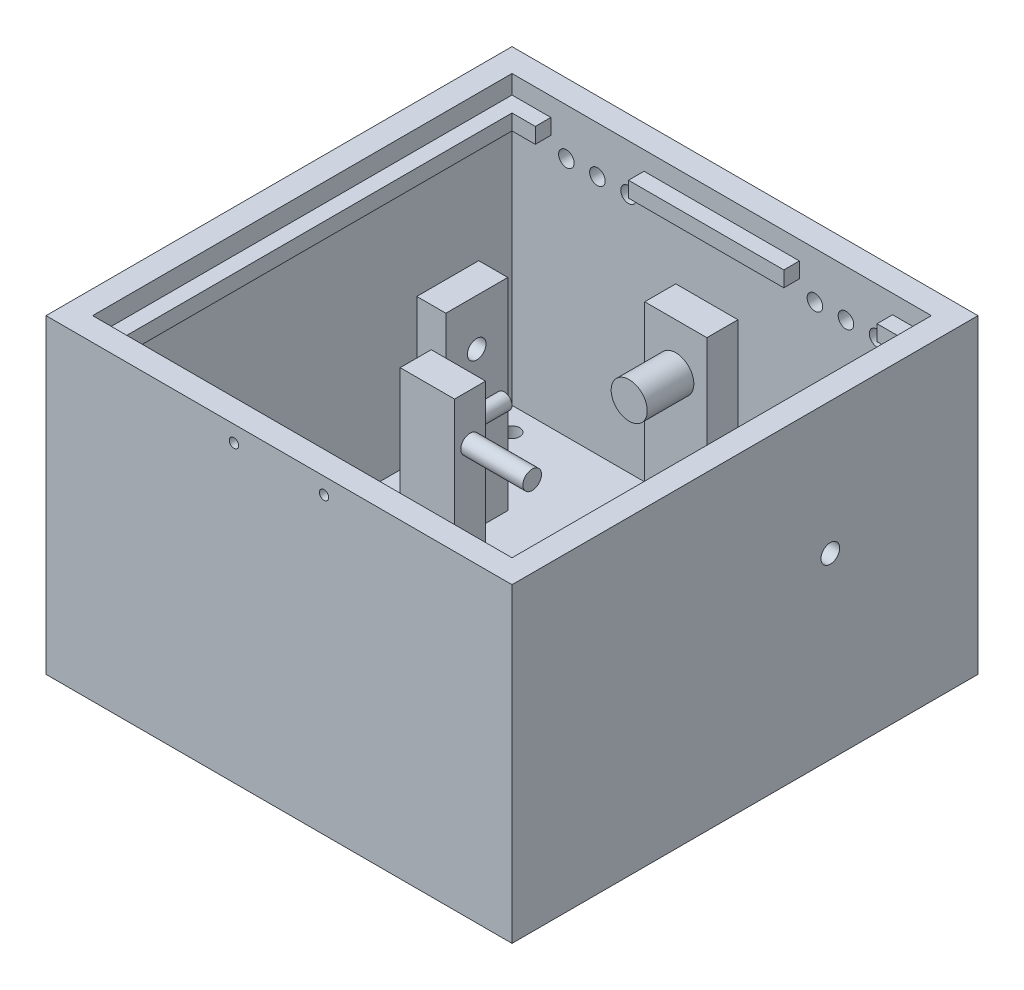
SolidWorks part; units mm, degrees
material "Cedar"
ref_plane "Front" through (0, 0, 0) normal (0, 0, 1) x (1, 0, 0)
ref_plane "Top" through (0, 0, 0) normal (0, 1, 0) x (1, 0, 0)
ref_plane "Right" through (0, 0, 0) normal (1, 0, 0) x (0, 0, -1)
sketch "Sketch1" plane through (0, 0, 0) normal (0, 1, 0) x (1, 0, 0)
  line L1 (-75, -75) -> (75, -75)
  line L2 (-75, -75) -> (-75, 75)
  line L3 (-75, 75) -> (75, 75)
  line L4 (75, -75) -> (75, 75)
  line L5 (-75, -75) -> (75, 75) construction
  line L6 (-75, 75) -> (75, -75) construction
  point P0 (0, 0)
  dimension "D1" = 150
  dimension "D2" = 150
extrude "Boss-Extrude1" add sketch "Sketch1" along normal blind 7.5
sketch "Sketch2" plane through (0, 7.5, 0) normal (0, 1, 0) x (1, 0, 0)
  line L1 (-67.5, -67.5) -> (67.5, -67.5)
  line L2 (-67.5, -67.5) -> (-67.5, 67.5)
  line L3 (-67.5, 67.5) -> (67.5, 67.5)
  line L4 (67.5, -67.5) -> (67.5, 67.5)
  line L5 (-67.5, -67.5) -> (67.5, 67.5) construction
  line L6 (-67.5, 67.5) -> (67.5, -67.5) construction
  line L7 (-75, -75) -> (75, -75)
  line L8 (-75, -75) -> (-75, 75)
  line L9 (-75, 75) -> (75, 75)
  line L10 (75, -75) -> (75, 75)
  line L11 (-75, -75) -> (75, 75) construction
  line L12 (-75, 75) -> (75, -75) construction
  point P0 (0, 0)
  point P5 (0, 0)
  dimension "D1" = 135
  dimension "D2" = 135
extrude "Boss-Extrude2" add sketch "Sketch2" along normal blind 92.5
sketch "Sketch3" plane through (0, 7.5, 0) normal (0, 1, 0) x (1, 0, 0)
  line L0 (0, -4.125) -> (0, 4.125) construction
  line L1 (-10, 62.7245) -> (10, 62.7245)
  line L2 (-10, 62.7245) -> (-10, 52.7245)
  line L3 (-10, 52.7245) -> (10, 52.7245)
  line L4 (10, 62.7245) -> (10, 52.7245)
  line L5 (-10, 62.7245) -> (10, 52.7245) construction
  line L6 (-10, 52.7245) -> (10, 62.7245) construction
  point P0 (0, 57.7245)
  dimension "D1" = 10
  dimension "D2" = 20
extrude "Boss-Extrude3" add sketch "Sketch3" along normal blind 65
sketch "Sketch4" plane through (0, 0, -52.7245) normal (0, 0, 1) x (1, 0, 0)
  line L0 (0, -4.125) -> (0, 4.125) construction
  line L2 (-10, 7.5) -> (10, 7.5) construction
  circle A0 centre (0, 57.5) radius 5.8075
  dimension "D1" = 11.615
  dimension "D2" = 50
extrude "Boss-Extrude4" add sketch "Sketch4" along normal blind 15 contours A0
sketch "Sketch5" plane through (0, 7.5, 0) normal (0, 1, 0) x (1, 0, 0)
  line L0 (-67.5, -67.5) -> (67.5, -67.5) construction
  line L1 (-48.1782, 37.4665) -> (-38.8218, 37.4665)
  line L2 (-48.1782, 37.4665) -> (-48.1782, 17.5335)
  line L3 (-48.1782, 17.5335) -> (-38.8218, 17.5335)
  line L4 (-38.8218, 37.4665) -> (-38.8218, 17.5335)
  line L5 (-48.1782, 37.4665) -> (-38.8218, 17.5335) construction
  line L6 (-48.1782, 17.5335) -> (-38.8218, 37.4665) construction
  line L7 (-67.5, 67.5) -> (-67.5, -67.5) construction
  point P0 (-43.5, 27.5)
  dimension "D1" = 95
  dimension "D2" = 9.3563
  dimension "D3" = 19.933
  dimension "D4" = 24
extrude "Boss-Extrude5" add sketch "Sketch5" along normal blind 65
sketch "Sketch6" plane through (-38.8218, 0, 0) normal (1, 0, 0) x (0, 0, -1)
  line L1 (17.5335, 7.5) -> (37.4665, 7.5) construction
  line L2 (37.4665, 72.5) -> (37.4665, 7.5) construction
  circle A0 centre (27.4665, 57.5) radius 3
  dimension "D1" = 6
  dimension "D2" = 50
  dimension "D3" = 10
sketch "Sketch7" plane through (0, 7.5, 0) normal (0, 1, 0) x (1, 0, 0)
  line L0 (-67.5, -67.5) -> (67.5, -67.5) construction
  line L1 (-23.5, 0) -> (-13.5, 0)
  line L2 (-23.5, 0) -> (-23.5, -5)
  line L3 (-23.5, -5) -> (-13.5, -5)
  line L4 (-13.5, 0) -> (-13.5, -5)
  line L5 (-23.5, 0) -> (-13.5, -5) construction
  line L6 (-23.5, -5) -> (-13.5, 0) construction
  line L7 (-67.5, 67.5) -> (-67.5, -67.5) construction
  line L9 (-23.5, 0) -> (-31, 0)
  line L10 (-23.5, 0) -> (-23.5, -5)
  line L11 (-23.5, -5) -> (-31, -5)
  line L12 (-31, 0) -> (-31, -5)
  point P0 (-18.5, -2.5)
  dimension "D1" = 5
  dimension "D2" = 10
  dimension "D3" = 65
  dimension "D4" = 49
  dimension "D5" = 7.5
  dimension "D6" = 5
extrude "Boss-Extrude7" add sketch "Sketch7" along normal blind 65 contours L9 L12 L11 L2 | L4 L1 L2 L3 region at (-18.5, 7.5, 2.5) region at (-27.25, 7.5, 2.5)
sketch "Sketch8" plane through (0, 0, 0) normal (0, 0, -1) x (-1, 0, 0)
  line L0 (13.5, 7.5) -> (31, 7.5) construction
  line L1 (13.5, 72.5) -> (13.5, 7.5) construction
  circle A0 centre (20, 57.5) radius 2.5
  dimension "D1" = 5
  dimension "D2" = 50
  dimension "D3" = 6.5
extrude "Boss-Extrude8" add sketch "Sketch8" along normal blind 17.5
sketch "Sketch9" plane through (-13.5, 0, 0) normal (1, 0, 0) x (0, 0, -1)
  line L0 (-5, 72.5) -> (-5, 7.5) construction
  line L1 (-5, 7.5) -> (0, 7.5) construction
  circle A0 centre (10, 57.5) radius 3
  dimension "D1" = 6
  dimension "D2" = 15
  dimension "D3" = 50
sketch "Sketch10" plane through (0, 7.5, 0) normal (0, 1, 0) x (1, 0, 0)
  line L1 (-31, 0) -> (-13.5, 0)
  line L2 (-31, 0) -> (-31, 5)
  line L3 (-31, 5) -> (-13.5, 5)
  line L4 (-13.5, 0) -> (-13.5, 5)
  dimension "D1" = 17.5
  dimension "D2" = 5
extrude "Boss-Extrude10" add sketch "Sketch10" along normal blind 65
sketch "Sketch12" plane through (-13.5, 0, 0) normal (1, 0, 0) x (0, 0, -1)
  line L2 (5, 7.5) -> (-5, 7.5) construction
  line L3 (75, 100) -> (75, 0) construction
  circle A0 centre (0, 57.5) radius 3
  dimension "D1" = 6
  dimension "D2" = 75
  dimension "D3" = 50
extrude "Boss-Extrude11" add sketch "Sketch12" along normal blind 20
extrude "Cut-Extrude1" cut sketch "Sketch6" against normal blind 10
sketch "Sketch13" plane through (0, 7.5, 0) normal (0, 1, 0) x (1, 0, 0)
  line L0 (67.5, 67.5) -> (-67.5, 67.5) construction
  line L1 (18.2, 21.5) -> (34.2, 21.5)
  line L2 (18.2, 21.5) -> (18.2, 33.5)
  line L3 (18.2, 33.5) -> (34.2, 33.5)
  line L4 (34.2, 21.5) -> (34.2, 33.5)
  line L5 (18.2, 21.5) -> (34.2, 33.5) construction
  line L6 (18.2, 33.5) -> (34.2, 21.5) construction
  line L7 (67.5, -67.5) -> (67.5, 67.5) construction
  point P0 (26.2, 27.5)
  dimension "D1" = 34
  dimension "D2" = 33.3
  dimension "D3" = 12
  dimension "D4" = 16
extrude "Boss-Extrude12" add sketch "Sketch13" along normal blind 12.5
sketch "Sketch14" plane through (0, 7.5, 0) normal (0, 1, 0) x (1, 0, 0)
  line L0 (-67.5, -67.5) -> (67.5, -67.5) construction
  line L1 (30, -7.5) -> (65, -7.5)
  line L2 (30, -7.5) -> (30, 33.5)
  line L3 (30, 33.5) -> (65, 33.5)
  line L4 (65, -7.5) -> (65, 33.5)
  line L5 (30, -7.5) -> (65, 33.5) construction
  line L6 (30, 33.5) -> (65, -7.5) construction
  point P0 (47.5, 13)
  dimension "D1" = 35
  dimension "D2" = 41
  dimension "D3" = 20
  dimension "D4" = 60
extrude "Boss-Extrude13" add sketch "Sketch14" along normal blind 31
sketch "Sketch15" plane through (75, 0, 0) normal (1, 0, 0) x (0, 0, -1)
  line L0 (75, 100) -> (75, 0) construction
  line L1 (-75, 0) -> (75, 0) construction
  circle A0 centre (27.4665, 57.5) radius 3
  dimension "D1" = 6
  dimension "D2" = 47.5335
  dimension "D3" = 57.5
extrude "Cut-Extrude2" cut sketch "Sketch15" against normal blind 10
sketch "Sketch16" plane through (0, 0, 67.5) normal (0, 0, -1) x (-1, 0, 0)
  line L0 (-75, 100) -> (-75, 0) construction
  line L1 (-75, 94) -> (75, 94)
  line L2 (-75, 94) -> (-75, 89)
  line L3 (-75, 89) -> (75, 89)
  line L4 (75, 94) -> (75, 89)
  dimension "D1" = 150
  dimension "D2" = 0
  dimension "D3" = 5
  dimension "D4" = 6
extrude "Boss-Extrude14" add sketch "Sketch16" along normal blind 5
sketch "Sketch17" plane through (0, 0, -67.5) normal (0, 0, 1) x (1, 0, 0)
  line L0 (-75, 100) -> (-75, 0) construction
  line L1 (-75, 94) -> (75, 94)
  line L2 (-75, 94) -> (-75, 89)
  line L3 (-75, 89) -> (75, 89)
  line L4 (75, 94) -> (75, 89)
  line L5 (75, 100) -> (75, 0) construction
  line L6 (-75, 100) -> (75, 100) construction
  line L8 (-55, 94) -> (-25, 94)
  line L9 (-55, 94) -> (-55, 89)
  line L10 (-55, 89) -> (-25, 89)
  line L11 (-25, 94) -> (-25, 89)
  line L12 (25, 94) -> (55, 94)
  line L13 (25, 94) -> (25, 89)
  line L14 (25, 89) -> (55, 89)
  line L15 (55, 94) -> (55, 89)
  line M4 (67.5, 7.5) -> (67.5, 100)
  line M6 (-67.5, 100) -> (-67.5, 7.5)
  dimension "D1" = 5
  dimension "D2" = 6
  dimension "D3" = 20
  dimension "D4" = 20
  dimension "D5" = 30
  dimension "D6" = 30
extrude "Boss-Extrude15" add sketch "Sketch17" along normal blind 5 contours L9 L1 L3 M6 | L13 L1 L11 L3 | L1 L15 L3 M4 region at (-61.25, 91.5, -67.5) region at (0, 91.5, -67.5) region at (61.25, 91.5, -67.5)
sketch "Sketch18" plane through (67.5, 0, 0) normal (-1, 0, 0) x (0, 0, 1)
  line L0 (-75, 100) -> (-75, 0) construction
  line L1 (-75, 94) -> (75, 94)
  line L2 (-75, 94) -> (-75, 89)
  line L3 (-75, 89) -> (75, 89)
  line L4 (75, 94) -> (75, 89)
  line L5 (75, 100) -> (75, 0) construction
  line L6 (-75, 100) -> (75, 100) construction
  dimension "D1" = 5
  dimension "D2" = 6
extrude "Boss-Extrude16" add sketch "Sketch18" along normal blind 5
sketch "Sketch19" plane through (-67.5, 0, 0) normal (1, 0, 0) x (0, 0, -1)
  line L0 (-75, 100) -> (-75, 0) construction
  line L1 (-75, 94) -> (75, 94)
  line L2 (-75, 94) -> (-75, 89)
  line L3 (-75, 89) -> (75, 89)
  line L4 (75, 94) -> (75, 89)
  line L5 (75, 100) -> (75, 0) construction
  line L6 (-75, 100) -> (75, 100) construction
  dimension "D1" = 5
  dimension "D2" = 6
extrude "Boss-Extrude17" add sketch "Sketch19" along normal blind 5
sketch "Sketch20" plane through (0, 0, -75) normal (0, 0, -1) x (-1, 0, 0)
  line L2 (-75, 100) -> (-75, 0) construction
  line L3 (-75, 100) -> (75, 100) construction
  line L4 (75, 100) -> (75, 0) construction
  circle A0 centre (-50, 85) radius 2.5
  circle A1 centre (-40, 85) radius 2.5
  circle A2 centre (-30, 85) radius 2.5
  circle A3 centre (30, 85) radius 2.5
  circle A4 centre (40, 85) radius 2.5
  circle A5 centre (50, 85) radius 2.5
  dimension "D1" = 5
  dimension "D2" = 5
  dimension "D3" = 5
  dimension "D4" = 5
  dimension "D5" = 5
  dimension "D6" = 5
  dimension "D7" = 10
  dimension "D8" = 10
  dimension "D9" = 10
  dimension "D10" = 10
  dimension "D11" = 25
  dimension "D12" = 25
  dimension "D13" = 15
  dimension "D14" = 15
  dimension "D15" = 15
  dimension "D16" = 15
  dimension "D17" = 15
  dimension "D18" = 15
extrude "Cut-Extrude3" cut sketch "Sketch20" against normal blind 10
sketch "Sketch21" plane through (0, 0, 0) normal (0, -1, 0) x (1, 0, 0)
  line L0 (-75, -75) -> (-75, 75) construction
  line L1 (75, -75) -> (-75, -75) construction
  line L2 (75, 75) -> (75, -75) construction
  line L3 (-75, 75) -> (75, 75) construction
  circle A0 centre (-60, 60) radius 2.5
  circle A1 centre (60, 60) radius 2.5
  circle A2 centre (-60, -60) radius 2.5
  circle A3 centre (60, -60) radius 2.5
  dimension "D1" = 5
  dimension "D2" = 5
  dimension "D3" = 5
  dimension "D4" = 5
  dimension "D5" = 15
  dimension "D6" = 15
  dimension "D7" = 15
  dimension "D8" = 15
  dimension "D9" = 15
  dimension "D10" = 15
  dimension "D11" = 15
  dimension "D12" = 15
extrude "Cut-Extrude4" cut sketch "Sketch21" against normal blind 10
sketch "Sketch22" plane through (0, 0, 75) normal (0, 0, 1) x (1, 0, 0)
  line L0 (-75, 100) -> (-75, 0) construction
  line L1 (-75, 100) -> (75, 100) construction
  circle A0 centre (-14.5, 94.75) radius 1.5
  circle A2 centre (14.5, 94.75) radius 1.5
  dimension "D1" = 3
  dimension "D2" = 3
  dimension "D3" = 5.25
  dimension "D4" = 60.5
  dimension "D5" = 29
  dimension "D6" = 5.25
extrude "Cut-Extrude5" cut sketch "Sketch22" against normal blind 5
sketch "Sketch23" plane through (0, 38.5, 0) normal (0, 1, 0) x (1, 0, 0)
  circle A0 centre (32.5, 8.61) radius 1
  circle A1 centre (32.5, 27.61) radius 1
  circle A2 centre (63, 31.61) radius 0.6
  circle A3 centre (57, 31.61) radius 0.6
  circle A4 centre (57, 7.31) radius 0.6
  circle A5 centre (63, 7.31) radius 0.6
  circle A6 centre (57, 28.9084) radius 0.6
  circle A7 centre (63, 28.91) radius 0.6
  circle A8 centre (63, 4.61) radius 0.6
  circle A9 centre (57, 4.61) radius 0.6
  dimension "D1" = 2
  dimension "D2" = 2
  dimension "D3" = 1.2
  dimension "D4" = 1.2
  dimension "D5" = 1.2
  dimension "D6" = 1.2
  dimension "D7" = 1.2
  dimension "D8" = 1.2
  dimension "D11" = 1.2
  dimension "D12" = 1.2
  dimension "D9" = 6
  dimension "D10" = 2.7016
  dimension "D13" = 2.7
  dimension "D14" = 6
extrude "Cut-Extrude6" cut sketch "Sketch23" against normal blind 4
sketch "Sketch24" plane through (0, 20, 0) normal (0, 1, 0) x (1, 0, 0)
  line L0 (18.2, 33.5) -> (18.2, 21.5) construction
  line L1 (18.2, 21.5) -> (30, 21.5) construction
  line L2 (30, 33.5) -> (18.2, 33.5) construction
  circle A0 centre (23.7, 24.4665) radius 0.75
  circle A1 centre (23.7, 30.5) radius 0.75
  circle A2 centre (19.7, 31.7165) radius 0.5
  circle A3 centre (19.7, 23.2) radius 0.5
  dimension "D1" = 1.5
  dimension "D2" = 1
  dimension "D5" = 1
  dimension "D6" = 1.5
  dimension "D3" = 1.5
  dimension "D4" = 1.7
  dimension "D7" = 5.5
  dimension "D8" = 3
extrude "Cut-Extrude7" cut sketch "Sketch24" against normal blind 4
